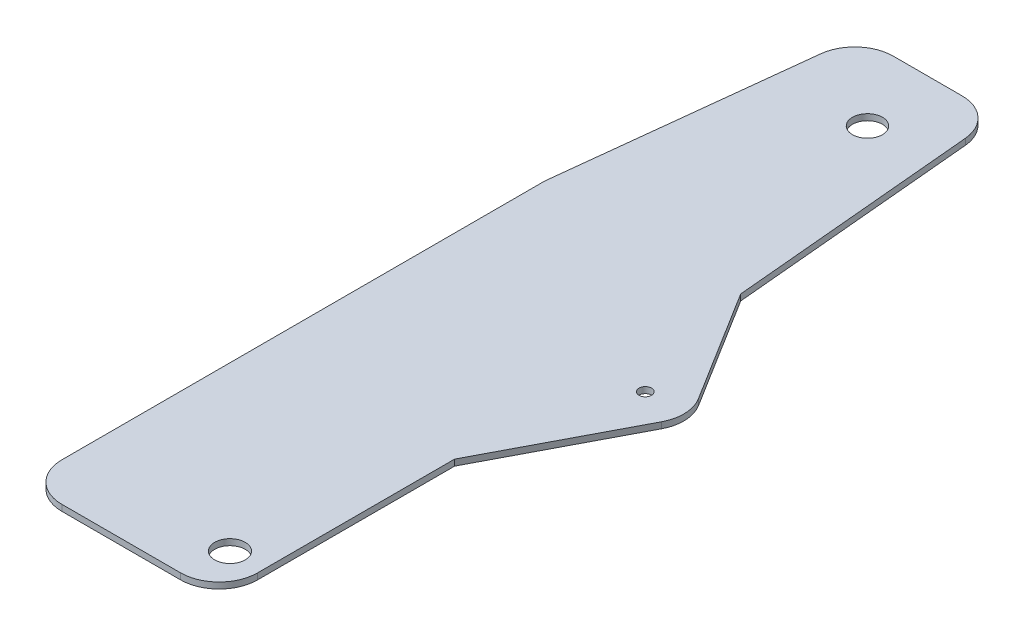
SolidWorks part; units mm, degrees
ref_plane "Front" through (0, 0, 0) normal (0, 0, 1) x (1, 0, 0)
ref_plane "Top" through (0, 0, 0) normal (0, 1, 0) x (1, 0, 0)
ref_plane "Right" through (0, 0, 0) normal (1, 0, 0) x (0, 0, -1)
sketch "Sketch1" plane through (0, 0, 0) normal (0, 1, 0) x (1, 0, 0)
  line L0 (10.4543, 228.6) -> (0, 135.3627)
  line L1 (0, 0) -> (50.8, 0)
  line L2 (0, 0) -> (0, 228.6)
  line L3 (0, 228.6) -> (50.8, 228.6)
  line L4 (50.8, 0) -> (50.8, 228.6)
  line L5 (42.3273, 228.6) -> (50.8, 135.3627)
  line L8 (50.8, 0) -> (24.327, 0)
  line L9 (50.8, 0) -> (50.8, -15)
  line L10 (50.8, -15) -> (24.327, -15)
  line L11 (24.327, 0) -> (24.327, -15)
  line L16 (50.8, 120.6192) -> (50.8, 104.4882)
  line L18 (50.8, 64.8791) -> (50.8, 87.4235)
  circle A2 centre (24.327, 25.5092) radius 5.969
  circle A3 centre (42.3273, 11.2956) radius 3.9601
  circle A12 centre (60.4, 101.001) radius 10
  circle A13 centre (29.5042, 189.5572) radius 3.9042
  dimension "D3" = 20
  dimension "D4" = 11.938
  dimension "D5" = 15
  dimension "D1" = 50.8
  dimension "D2" = 228.6
extrude "Boss-Extrude1" add sketch "Sketch1" along normal blind 1.5875 contours L1 L4 L3 L0 L2 region at (25.4775, 0, -108.4064)
sketch "Sketch4" plane through (0, 0, -228.6) normal (0, 0, -1) x (-1, 0, 0)
  line L1 (-61.3109, 11.9192) -> (4.9615, 11.9192)
  line L2 (-61.3109, 11.9192) -> (-61.3109, -15.8811)
  line L3 (-61.3109, -15.8811) -> (4.9615, -15.8811)
  line L4 (4.9615, 11.9192) -> (4.9615, -15.8811)
extrude "Cut-Extrude2" cut sketch "Sketch4" against normal blind 20
sketch "Sketch5" plane through (0, 0, 0) normal (0, -1, 0) x (1, 0, 0)
  circle A0 centre (24.327, -25.5092) radius 6.6837
extrude "Boss-Extrude2" add sketch "Sketch5" against normal blind 1.5875
fillet "Fillet3" radius 10 1 edges at (44.1447, 0.7937, -208.6)
fillet "Fillet4" radius 10 3 edges at (50.8, 0.7937, 0) (0, 0.7937, 0) (8.2118, 0.7937, -208.6)
sketch "Sketch6" plane through (0, 1.5875, 0) normal (0, 1, 0) x (1, 0, 0)
  line L0 (68.8909, 106.2834) -> (50.8, 135.3627)
  line L1 (50.8, 135.3627) -> (50.8, 103.801)
  line L2 (69.2582, 96.3607) -> (50.8, 61.1242)
  line L3 (50.8, 10) -> (50.8, 98.201) construction
  line L4 (50.8, 61.1242) -> (50.8, 96.3607)
  line L5 (50.8, 96.3607) -> (50.8, 98.201)
  circle A0 centre (60.4, 101.001) radius 10
  line M4 (50.8, 10) -> (50.8, 98.201)
  arc M5 (50.8, 98.201) -> (50.8, 103.801) centre (60.4, 101.001) cw
  line M6 (50.8, 103.801) -> (50.8, 135.3627)
extrude "Boss-Extrude3" add sketch "Sketch6" against normal blind 1.5875 contours A0 L0 M6 | A0 M5 | A0 L2 M4 region at (55.8248, 1.5875, -118.0301) region at (60.4, 1.5875, -101.001) region at (56.0341, 1.5875, -82.1407)
sketch "Sketch7" plane through (0, 1.5875, 0) normal (0, 1, 0) x (1, 0, 0)
  circle A0 centre (60.4, 101.001) radius 1.6271
extrude "Cut-Extrude3" cut sketch "Sketch7" against normal blind 1.5875
equation "\"7i\"=101.6"
